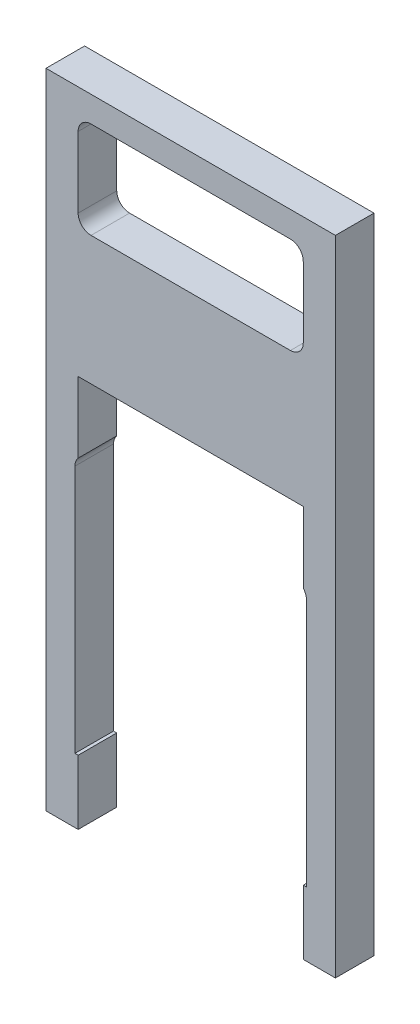
SolidWorks part; units mm, degrees
ref_plane "Front Plane" through (0, 0, 0) normal (0, 0, 1) x (1, 0, 0)
ref_plane "Top Plane" through (0, 0, 0) normal (0, 1, 0) x (1, 0, 0)
ref_plane "Right Plane" through (0, 0, 0) normal (1, 0, 0) x (0, 0, -1)
sketch "Sketch1" plane through (0, 0, 0) normal (0, 0, 1) x (1, 0, 0)
  line L1 (-28.575, -63.5) -> (28.575, -63.5)
  line L2 (-28.575, -63.5) -> (-28.575, 63.5)
  line L3 (-28.575, 63.5) -> (28.575, 63.5)
  line L4 (28.575, -63.5) -> (28.575, 63.5)
  line L5 (-28.575, -63.5) -> (28.575, 63.5) construction
  line L6 (-28.575, 63.5) -> (28.575, -63.5) construction
  point P0 (0, 0)
  dimension "D1" = 57.15
  dimension "D2" = 127
extrude "Boss-Extrude1" add sketch "Sketch1" along normal blind 7.62
sketch "Sketch2" plane through (0, 0, 7.62) normal (0, 0, 1) x (1, 0, 0)
  line L0 (0, 0) -> (0, -63.5) construction
  line L1 (-28.575, -63.5) -> (28.575, -63.5) construction
  line L2 (28.575, 63.5) -> (-28.575, 63.5) construction
  line L3 (-22.225, 58.42) -> (22.225, 58.42)
  line L4 (-22.225, 58.42) -> (-22.225, -63.5)
  line L5 (-22.225, -63.5) -> (22.225, -63.5)
  line L6 (22.225, 58.42) -> (22.225, -63.5)
  line L7 (-22.225, 58.42) -> (22.225, -63.5) construction
  line L8 (-22.225, -63.5) -> (22.225, 58.42) construction
  point P5 (0, -2.54)
  dimension "D1" = 44.45
  dimension "D2" = 5.08
extrude "Cut-Extrude1" cut sketch "Sketch2" against normal through all
sketch "Sketch4" plane through (0, 0, 7.62) normal (0, 0, 1) x (1, 0, 0)
  line L0 (-22.225, 58.42) -> (-22.225, -63.5) construction
  line L1 (-22.86, -50.8) -> (22.86, -50.8)
  line L2 (-22.86, -50.8) -> (-22.86, 0)
  line L3 (-22.86, 0) -> (22.86, 0)
  line L4 (22.86, -50.8) -> (22.86, 0)
  line L5 (22.225, -63.5) -> (22.225, 58.42) construction
  line L6 (-28.575, -63.5) -> (-22.225, -63.5) construction
  dimension "D1" = 0.635
  dimension "D2" = 0.635
  dimension "D3" = 12.7
  dimension "D4" = 50.8
extrude "Cut-Extrude2" cut sketch "Sketch4" against normal through all
sketch "Sketch5" plane through (0, 0, 7.62) normal (0, 0, 1) x (1, 0, 0)
  line L0 (22.225, 0) -> (22.225, 58.42) construction
  line L1 (-22.225, 13.97) -> (22.225, 13.97)
  line L2 (-22.225, 13.97) -> (-22.225, 39.37)
  line L3 (-22.225, 39.37) -> (22.225, 39.37)
  line L4 (22.225, 13.97) -> (22.225, 39.37)
  line L5 (22.225, 58.42) -> (-22.225, 58.42) construction
  point P7 (0, 0)
  dimension "D1" = 25.4
  dimension "D2" = 19.05
extrude "Boss-Extrude2" add sketch "Sketch5" against normal up to surface (7.62 mm away) up to face at (0, -13.335, 0)
fillet "Fillet1" radius 2.54 6 edges at (-22.225, 58.42, 3.81) (22.225, 58.42, 3.81) (22.86, 0, 3.81) (-22.86, 0, 3.81) (22.225, 39.37, 3.81) (-22.225, 39.37, 3.81)
